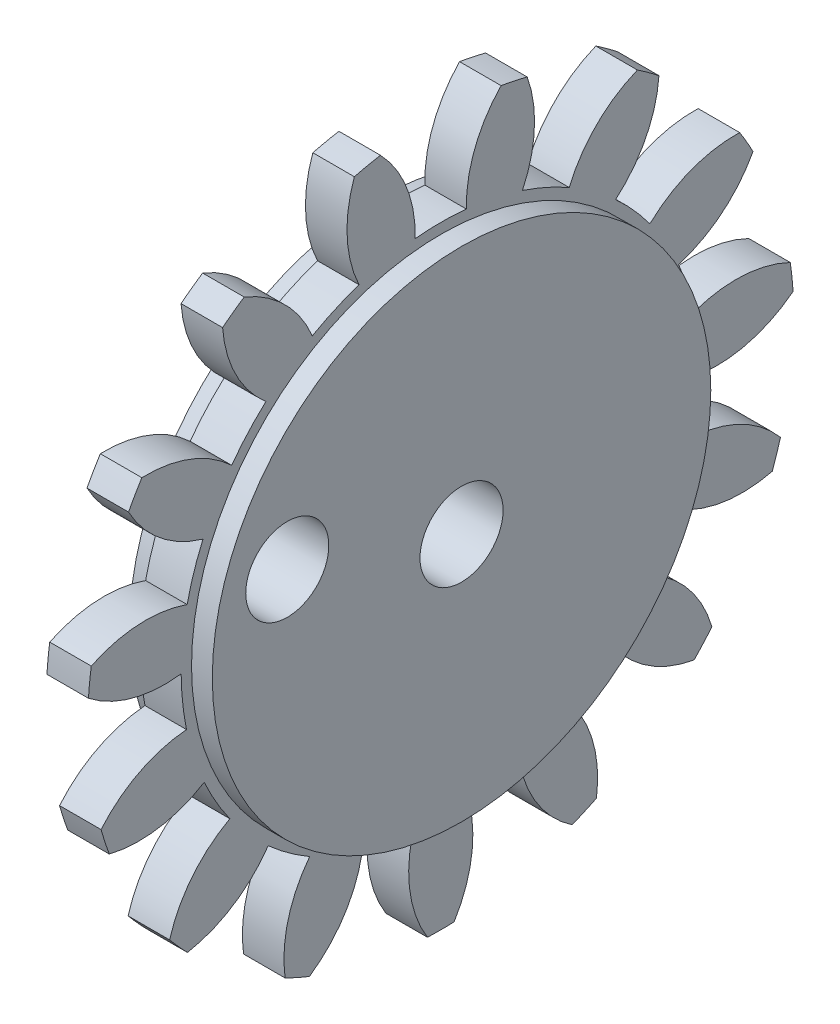
SolidWorks part; units mm, degrees
ref_plane "Plane1" through (0, 0, 0) normal (0, 0, 1) x (1, 0, 0)
ref_plane "Plane2" through (0, 0, 0) normal (0, 1, 0) x (1, 0, 0)
ref_plane "Plane3" through (0, 0, 0) normal (1, 0, 0) x (0, 0, -1)
other "Configuration Table"
sketch "HoldingSke" plane through (0, 0, 0) normal (0, 1, 0) x (1, 0, 0)
  line L0 (0, 0) -> (98.1381, -26.296)
  line L1 (-15, 0) -> (100, 0) construction
  line L2 (0, 0) -> (-2.1039, 2.3779)
  line L3 (0, 0) -> (-11.863, 4.5341)
  line L4 (0, 0) -> (8.3417, 2.2352)
  line L5 (0, 0) -> (-11.8993, -4.4381)
  line L6 (0, 0) -> (-5.2639, -3.5516)
  line L7 (-2.1039, 2.3779) -> (0.6298, 14.7802)
  line L8 (-76.2, 54.61) -> (-61.976, 54.61)
  line L9 (-67.7845, 28.3722) -> (-49.3413, 33.142)
  line L10 (-76.2, 71.12) -> (104.1128, 71.12)
  line L11 (0, 0) -> (-6.35, 0)
  line L12 (-76.2, 101.6) -> (-75.9714, 101.6)
  line L13 (24.9733, 27.94) -> (52.9518, 28.4284)
  line L14 (24.9733, 27.94) -> (24.9746, 27.94)
  line L15 (24.9733, 27.94) -> (100.4006, 29.5858)
  circle A0 centre (0, 0) radius 6.35
  circle A1 centre (0, 0) radius 38.1
  circle A2 centre (0, 0) radius 38.1
  circle A3 centre (0, 0) radius 6.35
  dimension "Num_teeth" = 15
  dimension "H" = 19.05
  dimension "Pitch_radius" = 180.3128
  dimension "Width" = 6.35
  dimension "Thickness" = 6.35
sketch "BasProSke" plane through (0, 0, 0) normal (0, 1, 0) x (1, 0, 0)
  line L0 (-10, 0) -> (60, 0) construction
  line L1 (0, 0) -> (0, 53.975)
  line L2 (0, 0) -> (6.35, 0)
  line L3 (6.35, 0) -> (6.35, 53.975)
  line L4 (6.35, 53.975) -> (0, 53.975)
  dimension "Thickness" = 6.35
  dimension "Diameter" = 107.95
revolve "Base-Revolve" add sketch "BasProSke" angle 360 about L0
sketch "TooCutSke" plane through (0, 0, 0) normal (1, 0, 0) x (0, 0, -1)
  line L1 (0, 0) -> (0, 107) construction
  line L2 (0, 0) -> (-5.3779, 47.3204) construction
  line L3 (0, 0) -> (-19.7119, 92.7371) construction
  line L4 (-5.3779, 47.3204) -> (-9.8559, 46.3685) construction
  arc A0 (3.9155, 39.4926) -> (-3.9155, 39.4926) centre (0, 0) ccw
  arc A1 (9.2414, 53.2038) -> (-9.2414, 53.2038) centre (0, 0) ccw
  circle A2 centre (0, 0) radius 47.625 construction
  circle A3 centre (0, 0) radius 46.108 construction
  arc A4 (-3.9155, 39.4926) -> (-9.2414, 53.2038) centre (-22.9591, 39.9854) ccw
  arc A5 (9.2414, 53.2038) -> (3.9155, 39.4926) centre (22.9591, 39.9854) ccw
extrude "ToothCut" cut sketch "TooCutSke" along normal through all
fillet "Breaks" [suppressed] radius 0.127 tangent propagation no
fillet "RootFillets" [suppressed] radius 1.5888
pattern_circular "TeethCuts" count 15 every 24 about axis through (-10, 0, 0) along (1, 0, 0) of "ToothCut", "RootFillets", "Breaks"
sketch "HubNeaOneSke" plane through (0, 0, 0) normal (-1, 0, 0) x (0, 0, 1)
  circle A0 centre (0, 0) radius 38.1
  dimension "Diameter" = 76.2
extrude "HubNearOne" [suppressed] add sketch "HubNeaOneSke" along normal blind 6.3501
sketch "HubNeaBotSke" plane through (0, 0, 0) normal (-1, 0, 0) x (0, 0, 1)
  circle A0 centre (0, 0) radius 38.1
  dimension "Diameter" = 76.2
extrude "HubNearBoth" add sketch "HubNeaBotSke" along normal blind 3.175
ref_plane "FarPln" through (6.35, 0, 0) normal (1, 0, 0) x (0, 0, -1)
sketch "HubFarSke" plane through (6.35, 0, 0) normal (1, 0, 0) x (0, 0, -1)
  circle A0 centre (0, 0) radius 38.1
  dimension "Diameter" = 76.2
extrude "HubFar" add sketch "HubFarSke" along normal blind 3.175
sketch "BorSke" plane through (0, 0, 0) normal (1, 0, 0) x (0, 0, -1)
  circle A0 centre (0, 0) radius 6.35
  dimension "Diameter" = 12.7
extrude "Bore" cut sketch "BorSke" along normal mid plane 25.4001
sketch "KeySke" plane through (0, 0, 0) normal (1, 0, 0) x (0, 0, -1)
  line L0 (-1.5875, 0) -> (-1.5875, 7.874)
  line L1 (-1.5875, 7.874) -> (1.5875, 7.874)
  line L2 (1.5875, 7.874) -> (1.5875, 0)
  line L3 (0, 0) -> (0, 34) construction
  line L4 (-1.5875, 0) -> (1.5875, 0)
  dimension "Width" = 3.175
extrude "Keyway" [suppressed] cut sketch "KeySke" along normal mid plane 25.4001
pattern_circular "Keyway2" [suppressed] count 2 every 90 about axis through (-10, 0, 0) along (1, 0, 0) reverse direction yes
sketch "Sketch1" plane through (-3.175, 0, 0) normal (-1, 0, 0) x (0, 0, 1)
  line L0 (0, 0) -> (27.6826, 4.2691) construction
  line L1 (0, 0) -> (46.7437, 26.9875) construction
  line L2 (0, 0) -> (37.7438, 12.2637) construction
  circle A0 centre (27.6826, 4.2691) radius 6.35 construction
  arc A1 (47.7296, 25.2029) -> (45.6911, 28.7336) centre (0, 0) ccw construction
  circle A2 centre (0, 0) radius 28.0098 construction
  arc A4 (38.7696, 8.48) -> (36.3498, 15.9277) centre (0, 0) ccw construction
  circle A5 centre (26.6389, 8.6555) radius 6.35
extrude "Cut-Extrude1" cut sketch "Sketch1" against normal through all
scale "Scale1" scale about centroid uniform scaling yes scale factor 0.75
equation "' \"Pitch@HoldingSke\" = 4"
equation "' \"Num_teeth@HoldingSke\" = 12"
equation "' \"Ap@HoldingSke\" =  20"
equation "' \"Ap@HoldingSke\" = 20"
equation "' \"Width@HoldingSke\" = 0.5"
equation "' \"Hub_dia@HoldingSke\"= 1"
equation "' \"Hub_dia@HoldingSke\" = 1"
equation "' \"Overall_len@HoldingSke\" = 1.0"
equation "' \"Bore@HoldingSke\" = 0.75"
equation "' \"T_dim@HoldingSke\" = 0.85"
equation "' \"Width@KeySke\" = 0.25"
equation "' \"Show_teeth@HoldingSke\" = 13"
equation "' \"Backlash@HoldingSke\" = 0.009"
equation "' \"Addendum_fac@HoldingSke\" = 1.0"
equation "' \"Dedendum_fac@HoldingSke\" = 1.25"
equation "' \"Dedendum_add@HoldingSke\" = 0.00005"
equation "' \"Clearance_fac@HoldingSke\" = 0.25"
equation "' \"Pitch@HoldingSke\" = 0.5"
equation "' \"Num_teeth@HoldingSke\" = 23"
equation "' \"Show_teeth@HoldingSke\" = 23"
equation "' \"Backlash@HoldingSke\" = 0.0375"
equation "\"Overcut_dia@TooCutSke\" = (\"Num_teeth@HoldingSke\" + 2 * \"Addendum_fac@HoldingSke\") / \"Pitch@HoldingSke\" + 0.002"
equation "\"Pitch_dia@TooCutSke\" = \"Num_teeth@HoldingSke\" / \"Pitch@HoldingSke\""
equation "\"Base_dia@TooCutSke\" = \"Num_teeth@HoldingSke\" / \"Pitch@HoldingSke\" * cos((\"Ap@HoldingSke\"  * 3.14159265 / 180))"
equation "\"Root_dia@TooCutSke\" = (\"Num_teeth@HoldingSke\" + 2) / \"Pitch@HoldingSke\" - 2 * (\"Addendum_fac@HoldingSke\" + \"Dedendum_fac@HoldingSke\") / \"Pitch@HoldingSke\" - \"Dedendum_add@HoldingSke\" * 2"
equation "\"Half_ang@TooCutSke\" = 180 / \"Num_teeth@HoldingSke\""
equation "\"Half_CT@TooCutSke\" = \"Num_teeth@HoldingSke\" / \"Pitch@HoldingSke\" * sin((3.14159265 / 2 / \"Num_teeth@HoldingSke\")) / 2 - 7 * \"Backlash@HoldingSke\" / 4"
equation "\"Flank_rad@TooCutSke\" = \"Num_teeth@HoldingSke\" / \"Pitch@HoldingSke\" / 5"
equation "\"Radius@RootFillets\" = \"Clearance_fac@HoldingSke\" / \"Pitch@HoldingSke\" + \"Dedendum_add@HoldingSke\""
equation "\"Break_rad@Breaks\" = 0.02 / \"Pitch@HoldingSke\""
equation "\"Thickness@HoldingSke\" = \"Width@HoldingSke\""
equation "\"OAL@HoldingSke\" = \"Thickness@HoldingSke\""
equation "\"MHD@HoldingSke\" = (\"Num_teeth@HoldingSke\" + 2) / \"Pitch@HoldingSke\" - 2 * (\"Addendum_fac@HoldingSke\" + \"Dedendum_fac@HoldingSke\")  / \"Pitch@HoldingSke\" - \"Dedendum_add@HoldingSke\" * 2"
equation "\"MBD@HoldingSke\" = (\"Num_teeth@HoldingSke\" + 2) / \"Pitch@HoldingSke\" - 2 * (\"Addendum_fac@HoldingSke\" + \"Dedendum_fac@HoldingSke\")  / \"Pitch@HoldingSke\" - \"Dedendum_add@HoldingSke\" * 2 - 0.002"
equation "\"MHD@HoldingSke\" = ((sgn( \"MHD@HoldingSke\" - \"Hub_dia@HoldingSke\" )-1)*( \"MHD@HoldingSke\" - \"Hub_dia@HoldingSke\" ))/-2+ \"Hub_dia@HoldingSke\""
equation "\"MBD@HoldingSke\" = ((sgn( \"MBD@HoldingSke\" - \"Bore@HoldingSke\" )-1)*( \"MBD@HoldingSke\" - \"Bore@HoldingSke\" ))/-2+ \"Bore@HoldingSke\""
equation "\"OAL@HoldingSke\" = ((sgn( \"OAL@HoldingSke\" - \"Overall_len@HoldingSke\" )+1)*( \"OAL@HoldingSke\" - \"Overall_len@HoldingSke\" ))/2 + \"Overall_len@HoldingSke\" + 0.000002"
equation "\"Num_teeth@TeethCuts\" = int( \"Show_teeth@HoldingSke\" ) + 1"
equation "\"Num_teeth@TeethCuts\" = ((sgn( \"Num_teeth@TeethCuts\" - \"Num_teeth@HoldingSke\" )-1)*( \"Num_teeth@TeethCuts\" - \"Num_teeth@HoldingSke\" ))/-2+ \"Num_teeth@HoldingSke\""
equation "\"Num_teeth@TeethCuts\" = ((sgn( \"Num_teeth@TeethCuts\" - 2.0)+1)*( \"Num_teeth@TeethCuts\" - 2.0))/2 +2.0"
equation "\"Angle@TeethCuts\" = 360.0 / \"Num_teeth@HoldingSke\""
equation "\"Diameter@BasProSke\" = (\"Num_teeth@HoldingSke\" + 2 * \"Addendum_fac@HoldingSke\") / \"Pitch@HoldingSke\""
equation "\"Thickness@BasProSke\"  = \"Thickness@HoldingSke\""
equation "' \"Fillet_rad@BasProSke\" =  \"Thickness@HoldingSke\" * 0.05"
equation "' \"Fillet_rad@BasProSke\" = \"Thickness@HoldingSke\" * 0.05"
equation "\"MHD@HoldingSke\" = ((sgn( \"MHD@HoldingSke\" - \"Root_dia@TooCutSke\" )-1)*( \"MHD@HoldingSke\" - \"Root_dia@TooCutSke\" ))/-2+ \"Root_dia@TooCutSke\""
equation "\"Diameter@HubNeaOneSke\" = \"MHD@HoldingSke\""
equation "\"Length@HubNearOne\" = \"OAL@HoldingSke\" - \"Thickness@BasProSke\""
equation "\"Diameter@HubNeaBotSke\" = \"MHD@HoldingSke\""
equation "\"Length@HubNearBoth\" = ( \"OAL@HoldingSke\" - \"Thickness@BasProSke\" ) / 2.0"
equation "\"Thickness@FarPln\" = \"Thickness@BasProSke\""
equation "\"Diameter@HubFarSke\" = \"MHD@HoldingSke\""
equation "\"Length@HubFar\" = ( \"OAL@HoldingSke\" - \"Thickness@BasProSke\" ) / 2.0"
equation "\"Diameter@BorSke\" = \"MBD@HoldingSke\""
equation "\"D1@Bore\" = \"OAL@HoldingSke\" * 2.0"
equation "\"D1@Keyway\" = \"OAL@HoldingSke\" * 2.0"
equation "\"Offset@KeySke\" = \"T_dim@HoldingSke\" - \"MBD@HoldingSke\" / 2.0"
